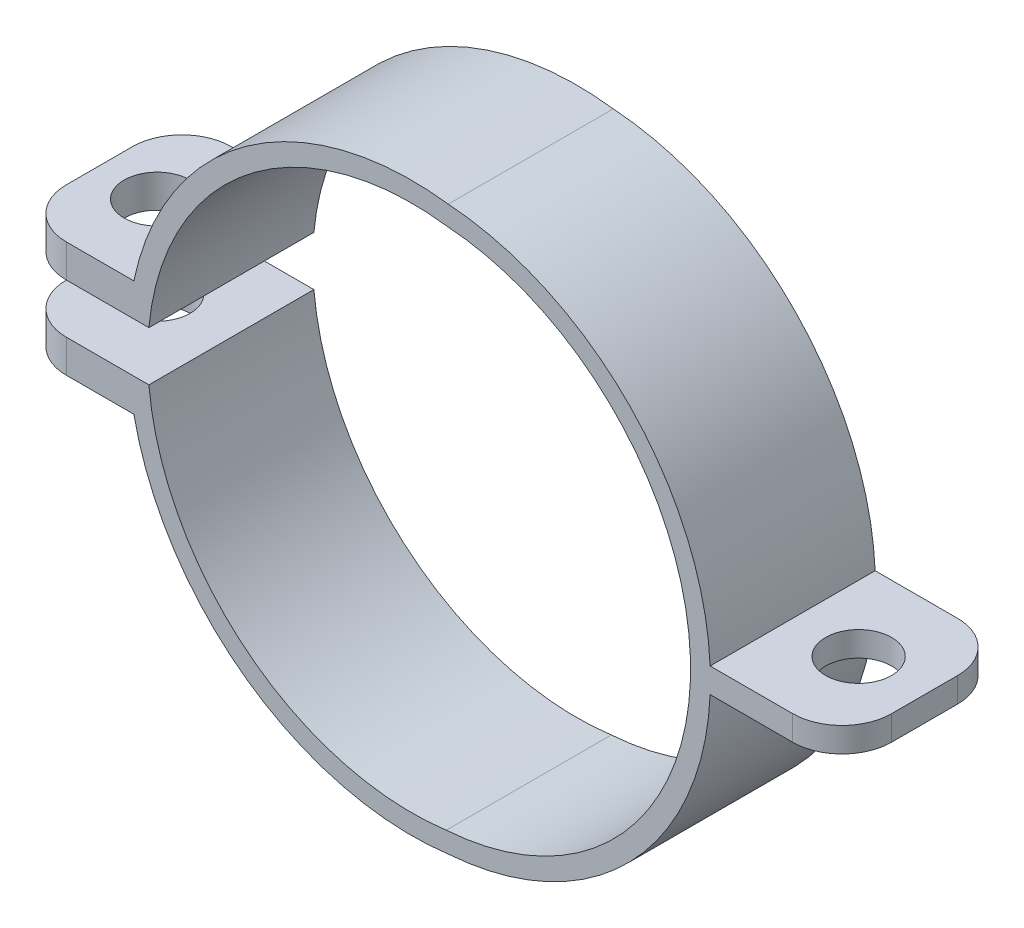
SolidWorks part; units mm, degrees
ref_plane "Front Plane" through (0, 0, 0) normal (0, 0, 1) x (1, 0, 0)
ref_plane "Top Plane" through (0, 0, 0) normal (0, 1, 0) x (1, 0, 0)
ref_plane "Right Plane" through (0, 0, 0) normal (1, 0, 0) x (0, 0, -1)
sketch "Sketch1" plane through (0, 0, 0) normal (0, 0, 1) x (1, 0, 0)
  line L0 (0, 0) -> (-32.5697, 0) construction
  line L1 (-16.9295, 1.5) -> (-24.9295, 1.5)
  line L2 (-24.9295, -1.5) -> (-16.9295, -1.5)
  line L3 (-24.9295, 1.5) -> (-24.9295, 3.5)
  line L4 (-24.9295, 3.5) -> (-17.8401, 3.5)
  line L5 (-24.9295, -1.5) -> (-24.9295, -3.5)
  line L6 (-24.9295, -3.5) -> (-17.8401, -3.5)
  arc A0 (1.095, -15.8622) -> (1.095, 15.8622) centre (0, 0) ccw
  arc A1 (1.095, 15.8622) -> (-16.9295, 1.5) centre (-1, 0) ccw
  arc A2 (1.215, 17.0568) -> (-17.8401, 3.5) centre (-1, 0) ccw
  arc A3 (1.215, -17.0568) -> (1.215, 17.0568) centre (0, 0) ccw
  arc A4 (-17.8401, -3.5) -> (1.215, -17.0568) centre (-1, 0) ccw
  arc A5 (1.215, 17.0568) -> (1.215, -17.0568) centre (-1, 0) ccw construction
  arc A6 (-16.9295, -1.5) -> (1.095, -15.8622) centre (-1, 0) ccw
  arc A7 (1.095, 15.8622) -> (1.095, -15.8622) centre (-1, 0) ccw construction
  dimension "D1" = 31.8
  dimension "D2" = 32
  dimension "D3" = 1
  dimension "D4" = 3
  dimension "D5" = 1.5
  dimension "D6" = 8
  dimension "D8" = 2
  dimension "D9" = 2
  dimension "D7" = 1.2
extrude "Boss-Extrude2" add sketch "Sketch1" along normal blind 5 and the other way blind 5
sketch "Sketch2" plane through (0, 3.5, 0) normal (0, 1, 0) x (1, 0, 0)
  line L0 (-21.4295, 0) -> (0, 0) construction
  line L1 (-24.9295, 5) -> (-24.9295, -5) construction
  circle A0 centre (-21.4295, 0) radius 2
  point P4 (-21.3676, 0)
  dimension "D1" = 4
  dimension "D2" = 3.5
extrude "Cut-Extrude1" cut sketch "Sketch2" against normal through all both and the other way through all
sketch "Sketch3" plane through (0, 0, 0) normal (0, 0, 1) x (1, 0, 0)
  line L0 (21.0835, 0) -> (0, 0) construction
  line L1 (25.0835, -0.75) -> (17.0835, -0.75)
  line L2 (25.0835, -0.75) -> (25.0835, 0.75)
  line L3 (25.0835, 0.75) -> (17.0835, 0.75)
  line L4 (17.0835, -0.75) -> (17.0835, 0.75)
  line L5 (25.0835, -0.75) -> (17.0835, 0.75) construction
  line L6 (25.0835, 0.75) -> (17.0835, -0.75) construction
  arc A0 (1.215, -17.0568) -> (1.215, 17.0568) centre (0, 0) ccw construction
  point P0 (21.0835, 0)
  dimension "D1" = 8
  dimension "D2" = 1.5
extrude "Boss-Extrude3" add sketch "Sketch3" along normal blind 5 and the other way blind 5
sketch "Sketch4" plane through (0, 0.75, 0) normal (0, 1, 0) x (1, 0, 0)
  line L0 (25.0835, 5) -> (25.0835, -5) construction
  line L1 (0, 0) -> (21.0835, 0) construction
  circle A0 centre (21.0835, 0) radius 2
  dimension "D1" = 4
  dimension "D2" = 4
extrude "Cut-Extrude2" cut sketch "Sketch4" against normal through all both and the other way through all
fillet "Fillet1" radius 3 6 edges at (-24.9295, -2.5, -5) (-24.9295, 2.5, -5) (-24.9295, -2.5, 5) (-24.9295, 2.5, 5) (25.0835, 0, 5) (25.0835, 0, -5)
